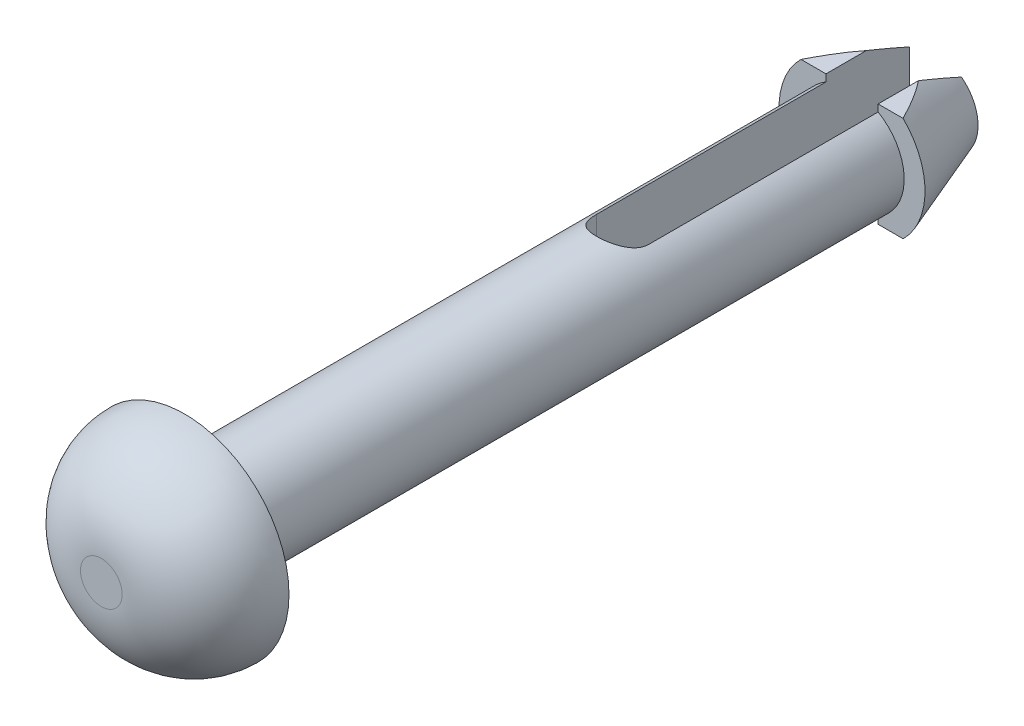
SolidWorks part; units mm, degrees
ref_plane "Front Plane" through (0, 0, 0) normal (0, 0, 1) x (1, 0, 0)
ref_plane "Top Plane" through (0, 0, 0) normal (0, 1, 0) x (1, 0, 0)
ref_plane "Right Plane" through (0, 0, 0) normal (1, 0, 0) x (0, 0, -1)
sketch "Sketch2" plane through (0, 0, 0) normal (0, 0, 1) x (1, 0, 0)
  circle A0 centre (0, 0) radius 2.5
  dimension "D1" = 5
extrude "Boss-Extrude1" add sketch "Sketch2" along normal blind 32
sketch "Sketch3" plane through (0, 0, 0) normal (0, 0, -1) x (-1, 0, 0)
  arc A0 (-2.9102, 1.9444) -> (-2.9102, -1.9444) centre (0, 0) ccw
  arc A1 (2.9102, -1.9444) -> (2.9102, 1.9444) centre (0, 0) ccw
  circle A2 centre (0, 0) radius 3.5
  circle M2 centre (0, 0) radius 2.5
  dimension "D1" = 7
extrude "Boss-Extrude2" add sketch "Sketch3" along normal blind 4 draft 20 contours A1 A2 A0 M2 | M2 region at (0, 3.401, 0) region at (0, 0, 0)
sketch "Sketch4" plane through (0, 0, 0) normal (0, 0, 1) x (1, 0, 0)
  line L0 (4.702, 2.5) -> (-6.1196, 2.5)
  line L1 (-6.1196, 2.5) -> (-4.7301, -2.5)
  line L2 (-4.7301, -2.5) -> (5.6003, -2.5)
  line L3 (5.6003, -2.5) -> (7.6285, -1.1685)
  line L4 (7.6285, -1.1685) -> (5.1441, -5.1266)
  line L5 (5.1441, -5.1266) -> (-5.5301, -4.7196)
  line L6 (-5.5301, -4.7196) -> (-7.7057, 3.5195)
  line L7 (-7.7057, 3.5195) -> (-2.5407, 4.8833)
  line L8 (-2.5407, 4.8833) -> (4.1616, 4.8248)
  line L9 (4.1616, 4.8248) -> (4.785, 2.4642)
  line L10 (4.785, 2.4642) -> (4.702, 2.5)
extrude "Cut-Extrude1" cut sketch "Sketch4" against normal blind 6
sketch "Sketch5" plane through (0, 2.5, 0) normal (0, 1, 0) x (1, 0, 0)
  line L0 (0, 19) -> (0, -11) construction
  line L4 (2.0441, 4) -> (-2.0441, 4) construction
  line L5 (1.25, 19) -> (1.25, -11)
  line L6 (-1.25, 19) -> (-1.25, -11)
  arc A2 (1.25, 19) -> (-1.25, 19) centre (0, 19) ccw
  arc A3 (-1.25, -11) -> (1.25, -11) centre (0, -11) ccw
  point P5 (0, 4)
  dimension "D2" = 15
  dimension "D1" = 1.25
extrude "Cut-Extrude2" cut sketch "Sketch5" against normal blind 6
sketch "Sketch6" plane through (0, 0, 32) normal (0, 0, 1) x (1, 0, 0)
  circle A0 centre (0, 0) radius 5
  dimension "D1" = 10
extrude "Boss-Extrude3" add sketch "Sketch6" along normal blind 4
fillet "Fillet1" radius 4 1 edges at (5, 0, 36)
